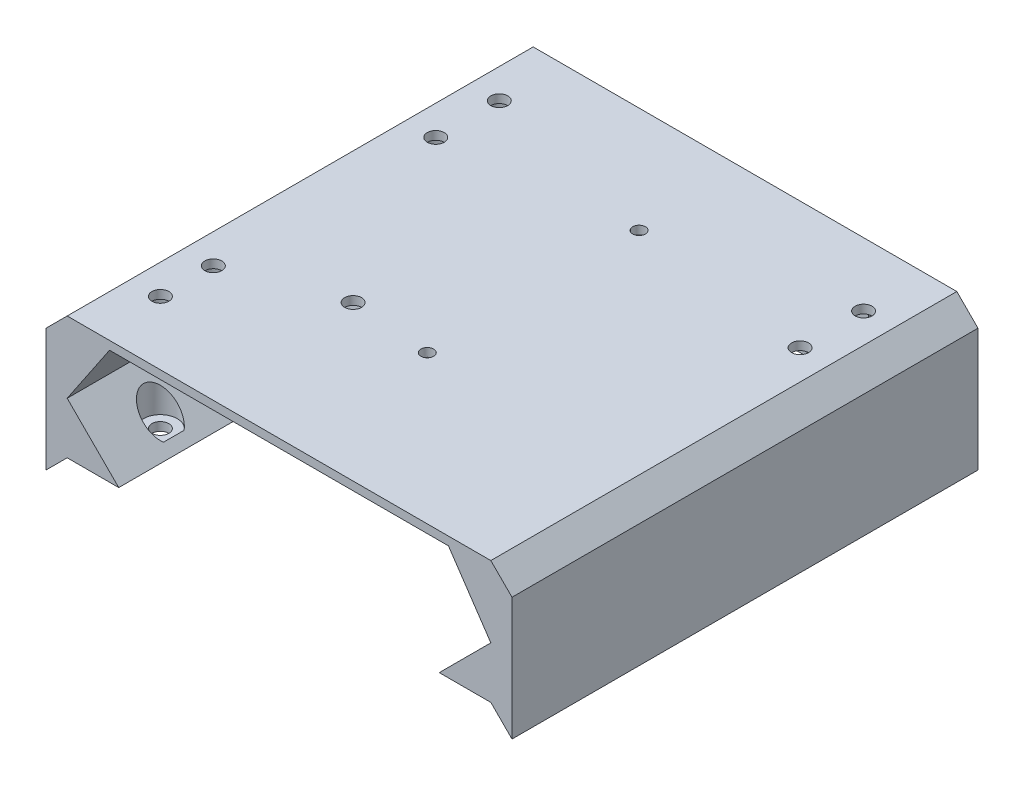
SolidWorks part; units mm, degrees
ref_plane "Front Plane" through (0, 0, 0) normal (0, 0, 1) x (1, 0, 0)
ref_plane "Top Plane" through (0, 0, 0) normal (0, 1, 0) x (1, 0, 0)
ref_plane "Right Plane" through (0, 0, 0) normal (1, 0, 0) x (0, 0, -1)
sketch "Sketch1" plane through (0, 0, 0) normal (0, 1, 0) x (1, 0, 0)
  line L1 (55, -55) -> (-55, -55)
  line L2 (55, -55) -> (55, 55)
  line L3 (55, 55) -> (-55, 55)
  line L4 (-55, -55) -> (-55, 55)
  line L5 (55, -55) -> (-55, 55) construction
  line L6 (55, 55) -> (-55, -55) construction
  point P0 (0, 0)
  dimension "D1" = 110
  dimension "D2" = 110
extrude "Boss-Extrude1" add sketch "Sketch1" along normal blind 2
sketch "Sketch2" plane through (0, 2, 0) normal (0, 1, 0) x (1, 0, 0)
  line L0 (-43, -40) -> (-43, -18.5) construction
  line L5 (-43, -18.5) -> (-19, -18.5) construction
  line L12 (-55, -55) -> (55, -55) construction
  line L13 (-55, 55) -> (-55, -55) construction
  circle A7 centre (-43, -40) radius 2
  circle A9 centre (-43, -27.5) radius 2
  circle A10 centre (-19, -18.5) radius 2
  dimension "D1" = 4
  dimension "D2" = 12.5
  dimension "D3" = 24
  dimension "D4" = 9
  dimension "D5" = 15
  dimension "D6" = 12
extrude "Cut-Extrude1" cut sketch "Sketch2" against normal through all
sketch "Sketch3" plane through (0, 0, 0) normal (0, -1, 0) x (1, 0, 0)
  line L0 (55, -55) -> (-55, -55) construction
  line L1 (-55, 55) -> (-50, 55)
  line L2 (-55, 55) -> (-55, -55)
  line L3 (-55, -55) -> (-50, -55)
  line L4 (-50, 55) -> (-50, -55)
  line L5 (55, 55) -> (50, 55)
  line L6 (55, 55) -> (55, -55)
  line L7 (55, -55) -> (50, -55)
  line L8 (50, 55) -> (50, -55)
  dimension "D1" = 5
extrude "Boss-Extrude2" add sketch "Sketch3" along normal blind 32
sketch "Sketch4" plane through (0, 2, 0) normal (0, 1, 0) x (1, 0, 0)
  line L0 (0, -20) -> (0, 30) construction
  line L2 (55, 55) -> (-55, 55) construction
  circle A0 centre (0, 30) radius 1.5
  circle A1 centre (0, -20) radius 1.5
  dimension "D1" = 3
  dimension "D3" = 25
  dimension "D2" = 50
extrude "Cut-Extrude2" cut sketch "Sketch4" against normal through all
sketch "Sketch5" plane through (0, 0, 0) normal (0, -1, 0) x (1, 0, 0)
  line L0 (50, -55) -> (-50, -55) construction
  line L1 (-55, 55) -> (-55, -55) construction
  line L2 (55, -55) -> (55, 55) construction
  circle A0 centre (-43, -25) radius 2
  circle A1 centre (-43, -40) radius 2
  circle A2 centre (43, -25) radius 2
  circle A3 centre (43, -40) radius 2
  dimension "D1" = 4
  dimension "D2" = 15
  dimension "D3" = 15
  dimension "D4" = 15
  dimension "D5" = 15
  dimension "D6" = 12
  dimension "D7" = 12
extrude "Cut-Extrude3" cut sketch "Sketch5" against normal through all
chamfer "Chamfer1" distance 10 angle 56 2 edges at (50, 0, 0) (-50, 0, 0) first distance on face at (-43, 0, -42)
sketch "Sketch6" plane through (0, 0, 0) normal (0, -1, 0) x (1, 0, 0)
  circle A0 centre (-43, 40) radius 4
  circle A1 centre (-43, 27.5) radius 4
  circle A2 centre (-43, -25) radius 4
  circle A3 centre (-43, -40) radius 4
  circle A4 centre (43, -25) radius 4
  circle A5 centre (43, -40) radius 4
  dimension "D1" = 8
extrude "Cut-Extrude4" cut sketch "Sketch6" along normal through all
chamfer "Chamfer2" distance 5 angle 45 2 edges at (55, 2, 0) (-55, 2, 0)
sketch "Sketch8" plane through (0, 0, -55) normal (0, 0, -1) x (-1, 0, 0)
  line L12 (-55, -32) -> (55, -32)
  line L24 (50, 2) -> (-50, 2)
  line L25 (-50, 2) -> (-55, -3)
  line L26 (-55, -3) -> (-55, -32)
  line L27 (-55, -32) -> (-50, -32)
  line L28 (-50, -32) -> (-50, -14.8256)
  line L29 (-50, -14.8256) -> (-40, 0)
  line L30 (-40, 0) -> (40, 0)
  line L31 (40, 0) -> (50, -14.8256)
  line L32 (50, -14.8256) -> (50, -32)
  line L33 (50, -32) -> (55, -32)
  line L34 (55, -32) -> (55, -3)
  line L35 (55, -3) -> (50, 2)
  line L36 (50, 2) -> (-50, 2)
  line L37 (-50, 2) -> (-55, -3)
  line L38 (-55, -3) -> (-55, -32)
  line L46 (55, -32) -> (55, -3)
  line L47 (55, -3) -> (50, 2)
  dimension "D1" = 0
extrude "Boss-Extrude3" add sketch "Sketch8" against normal blind 2
sketch "Sketch9" plane through (0, 0, -55) normal (0, 0, -1) x (-1, 0, 0)
  line L0 (-33.375, -8) -> (-33.375, -20) construction
  line L1 (-31.125, -8) -> (-31.125, -20)
  line L2 (-35.625, -8) -> (-35.625, -20)
  line L4 (-50, 2) -> (50, 2) construction
  arc A0 (-31.125, -8) -> (-35.625, -8) centre (-33.375, -8) ccw
  arc A1 (-35.625, -20) -> (-31.125, -20) centre (-33.375, -20) ccw
  point P2 (-33.375, -14)
  dimension "D1" = 4.5
  dimension "D2" = 33.375
  dimension "D3" = 10
  dimension "D4" = 12
extrude "Cut-Extrude5" cut sketch "Sketch9" against normal blind 2
mirror "Mirror1" about plane through (0, 0, 0) normal (1, 0, 0) of "Cut-Extrude5"
chamfer "Chamfer3" distance 5 angle 45 2 edges at (50, -32, 1) (-50, -32, 1)
sketch "Sketch10" plane through (0, 0, -53) normal (0, 0, 1) x (1, 0, 0)
  line L0 (-50, -27) -> (50, -27)
  line L8 (-40, 0) -> (-50, -14.8256)
  line L9 (-50, -14.8256) -> (-50, -27)
  line L10 (-50, -27) -> (-55, -32)
  line L11 (-55, -32) -> (55, -32)
  line L12 (55, -32) -> (50, -27)
  line L13 (50, -27) -> (50, -14.8256)
  line L14 (50, -14.8256) -> (40, 0)
  line L15 (40, 0) -> (-40, 0)
  line L18 (-50, -27) -> (-55, -32)
  line L19 (-55, -32) -> (55, -32)
  line L20 (55, -32) -> (50, -27)
  dimension "D1" = 0
extrude "Cut-Extrude6" cut sketch "Sketch10" against normal blind 2
sketch "Sketch11" plane through (0, 0, 55) normal (0, 0, 1) x (1, 0, 0)
  line L0 (-50, -14.8256) -> (-37.8256, -27)
  line L1 (50, -27) -> (-50, -27) construction
  line L2 (-37.8256, -27) -> (-50, -27)
  line L3 (-50, -27) -> (-50, -14.8256)
  dimension "D1" = 45
extrude "Boss-Extrude4" add sketch "Sketch11" against normal up to surface (108 mm away) up to face at (0, -13.9419, -53)
sketch "Sketch12" plane through (0, 0, 0) normal (0, 1, 0) x (1, 0, 0)
  circle A0 centre (-43, -40) radius 2
  circle A1 centre (-43, -27.5) radius 2
  circle A2 centre (-43, 25) radius 2
  circle A3 centre (-43, 40) radius 2
  circle A4 centre (-43, -40) radius 2 construction
extrude "Cut-Extrude7" cut sketch "Sketch12" against normal through all
sketch "Sketch13" plane through (0, 0, 0) normal (0, -1, 0) x (1, 0, 0)
  circle A0 centre (-43, 40) radius 4
  circle A1 centre (-43, 27.5) radius 4
  circle A2 centre (-43, -25) radius 4
  circle A3 centre (-43, -40) radius 4
  arc A4 (-40, -37.3542) -> (-40, -42.6458) centre (-43, -40) ccw construction
extrude "Cut-Extrude8" cut sketch "Sketch13" along normal offset from surface (25 mm away) 2 up to face at (-43, -27, 42)
mirror "Mirror2" about plane through (0, 0, 0) normal (1, 0, 0) of "Cut-Extrude8", "Boss-Extrude4", "Cut-Extrude7"
